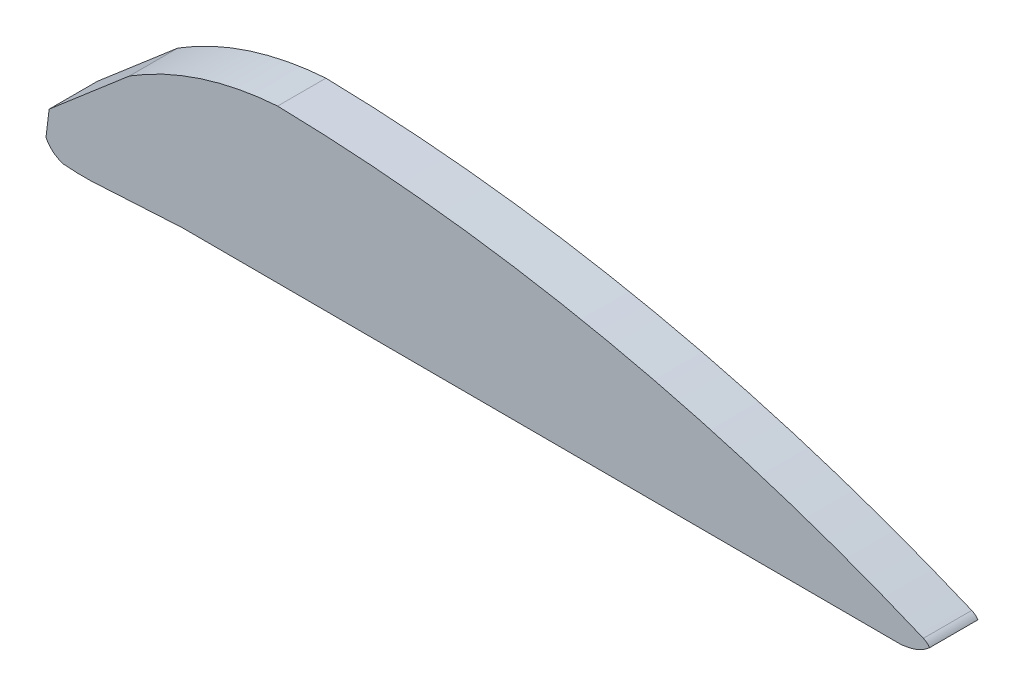
SolidWorks part; units mm, degrees
ref_plane "Ön Düzlem" through (0, 0, 0) normal (0, 0, 1) x (1, 0, 0)
ref_plane "Üst Düzlem" through (0, 0, 0) normal (0, 1, 0) x (1, 0, 0)
ref_plane "Sağ Düzlem" through (0, 0, 0) normal (1, 0, 0) x (0, 0, -1)
sketch "Çizim1" plane through (0, 0, 0) normal (0, 0, 1) x (1, 0, 0)
  line L0 (0, 0) -> (640, 0) construction
  line L1 (879.6322, -155.9159) -> (839.3184, -646.2615) construction
  line L2 (167.7372, 103.5679) -> (166.4581, -8.4248) construction
  line L3 (2.2808, 18.9265) -> (640, 0) construction
  line L4 (619.4948, -8.4248) -> (98.9268, -7.2516)
  line L5 (2.2808, 18.9265) -> (623.7297, -7.2516) construction
  line L6 (43.5044, -10.3545) -> (98.9268, -7.2516)
  line L7 (0, 0) -> (2.2808, 18.9265)
  line L8 (2.2808, 18.9265) -> (60.4579, 68.8095)
  arc A0 (0, 0) -> (12.5532, -10.3545) centre (18.0339, 9.0768) ccw
  arc A1 (12.5532, -10.3545) -> (43.5044, -10.3545) centre (28.0288, 166.585) ccw
  arc A2 (60.4579, 68.8095) -> (167.7372, 103.5679) centre (183.1128, -126.8223) cw
  arc A3 (167.7372, 103.5679) -> (635.4592, 3.5999) centre (140.3955, -1168.5097) cw
  arc A4 (635.4592, 3.5999) -> (640, 0) centre (631.2432, -6.3818) cw
  arc A5 (623.9898, -7.6107) -> (640, 0) centre (619.6031, 22.2626) ccw
  arc A6 (619.4948, -8.4248) -> (623.9898, -7.6107) centre (611.1273, 50.5886) ccw
  dimension "D1" = 640
  dimension "D2" = 112
  dimension "D3" = 1.7
  dimension "D4" = 638
  dimension "D5" = 622
base flange "Taban-Flanş1" sketch "Çizim1" thickness 35 reverse thickness direction yes parameters "D1"=8
sketch "Büküm-Çizgileri1" [suppressed] plane through (0, 0, 0) normal (0, 1, 0) x (1, 0, 0)
sketch "Sınırlandırma-Kutusu1" [suppressed] plane through (0, 0, 0) normal (0, 1, 0) x (1, 0, 0)
sheet metal parameters "Sac-Levha1" thickness 35 parameters "D1"=8
flat pattern "Düz-Çoğaltma1" [suppressed]
sketch "Büküm-Çizgileri2" plane through (0, 0, 0) normal (0, 1, 0) x (1, 0, 0)
sketch3d "Sınırlandırma-Kutusu2" [suppressed]
  line L0 (17.9848, -20.2317, 0) -> (-622.0028, -17.4111, 0) construction
  line L1 (18.4871, 93.7498, 0) -> (-621.5004, 96.5705, 0) construction
  line L2 (17.9848, -20.2317, 0) -> (18.4871, 93.7498, 0) construction
  line L3 (-622.0028, -17.4111, 0) -> (-621.5004, 96.5705, 0) construction
